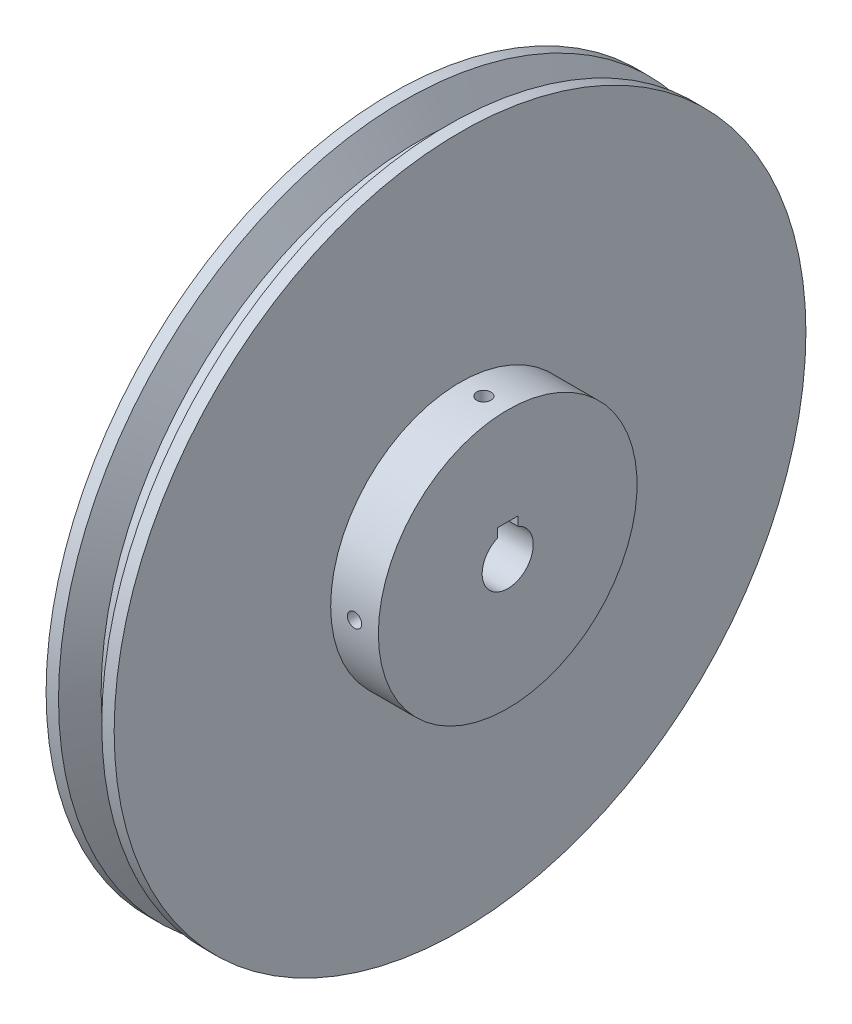
SolidWorks part; units mm, degrees
ref_plane "Front" through (0, 0, 0) normal (0, 0, 1) x (1, 0, 0)
ref_plane "Top" through (0, 0, 0) normal (0, 1, 0) x (1, 0, 0)
ref_plane "Right" through (0, 0, 0) normal (1, 0, 0) x (0, 0, -1)
sketch "Croquis1" plane through (0, 0, 0) normal (0, 0, 1) x (1, 0, 0)
  line L0 (0, 0) -> (34, 0)
  line L1 (34, 0) -> (34, 38)
  line L2 (34, 38) -> (20, 38)
  line L3 (20, 38) -> (20, 101.6)
  line L5 (0, 101.6) -> (0, 0)
  line L6 (3.65, 101.6) -> (0, 101.6)
  line L9 (8.2327, 93.6625) -> (11.7673, 93.6625)
  line L11 (3.65, 101.6) -> (14.0804, 97.669) construction
  line L12 (5.9196, 97.669) -> (16.35, 101.6) construction
  line L13 (16.35, 101.6) -> (20, 101.6)
  line L14 (3.65, 101.6) -> (8.2327, 93.6625)
  line L15 (10, 93.6625) -> (10, 99.2068) construction
  line L16 (16.35, 101.6) -> (11.7673, 93.6625)
  point P11 (10, 99.2068)
  dimension "D1" = 20
  dimension "D2" = 14
  dimension "D3" = 101.6
  dimension "D4" = 38
  dimension "D5" = 60
  dimension "D6" = 12.7
  dimension "D7" = 7.9375
revolve "Revolución1" add sketch "Croquis1" angle 360 about L0
sketch "Croquis2" plane through (34, 0, 0) normal (1, 0, 0) x (0, 0, -1)
  line L0 (0, 9.5) -> (0, 7.5) construction
  line L1 (-3, 9.5) -> (3, 9.5)
  line L2 (3, 9.5) -> (3, 6.8739)
  line L4 (0, 7.5) -> (0, 5.5) construction
  line L5 (-3, 9.5) -> (-3, 6.8739)
  arc A0 (-3, 6.8739) -> (3, 6.8739) centre (0, 0) ccw
  dimension "D1" = 15
  dimension "D2" = 4
  dimension "D3" = 3
  dimension "D4" = 6
extrude "Cortar-Extruir1" cut sketch "Croquis2" against normal up to surface (34 mm away) up to face at (0, 0, 101.6)
hole_wizard "Perforador para roscar para macho de roscar para M51" positions "Croquis3D1" profile "Croquis3" hole size "M5" standard "ISO"
sketch3d "Croquis3D1"
  line L0 (0, 0, 0) -> (0, 38, 0) construction
  line L2 (0, 0, 0) -> (0, 0, 38) construction
  point P0 (27, 0, 38)
  point P2 (27, 38, 0)
  dimension "D1" = 7
  dimension "D2" = 7
sketch "Croquis3" plane through (27, 0, 38) normal (1, 0, 0) x (0, -1, 0)
  line L0 (0, 0) -> (0, 41.2618)
  line L1 (0, 41.2618) -> (2.1, 40)
  line L2 (2.1, 40) -> (2.1, 0)
  line L5 (2.1, 0) -> (0, 0)
  line L10 (0, 41.2618) -> (-2.1, 40) construction
  line L11 (0, -6.35) -> (0, 107.95) construction
  dimension "Diámetro de taladro" = 4.2
  dimension "Profundidad de taladro" = 40
  dimension "Ángulo de perforador" = 118
cosmetic thread "Rosca cosmética1" parameters "D2"=5
cosmetic thread "Rosca cosmética2" parameters "D2"=5
